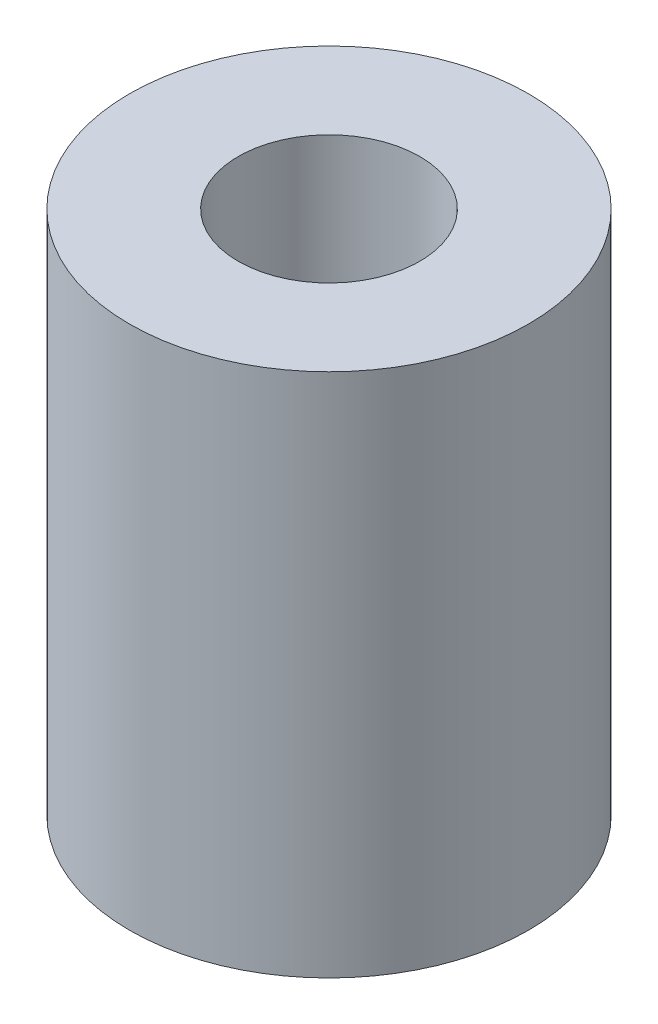
SolidWorks part; units mm, degrees
ref_plane "Front Plane" through (0, 0, 0) normal (0, 0, 1) x (1, 0, 0)
ref_plane "Top Plane" through (0, 0, 0) normal (0, 1, 0) x (1, 0, 0)
ref_plane "Right Plane" through (0, 0, 0) normal (1, 0, 0) x (0, 0, -1)
sketch "Sketch1" plane through (0, 0, 0) normal (0, 1, 0) x (1, 0, 0)
  circle A0 centre (0, 0) radius 2.413
  circle A1 centre (0, 0) radius 1.0983
  dimension "D1" = 4.826
extrude "Boss-Extrude1" add sketch "Sketch1" along normal blind 6.35
